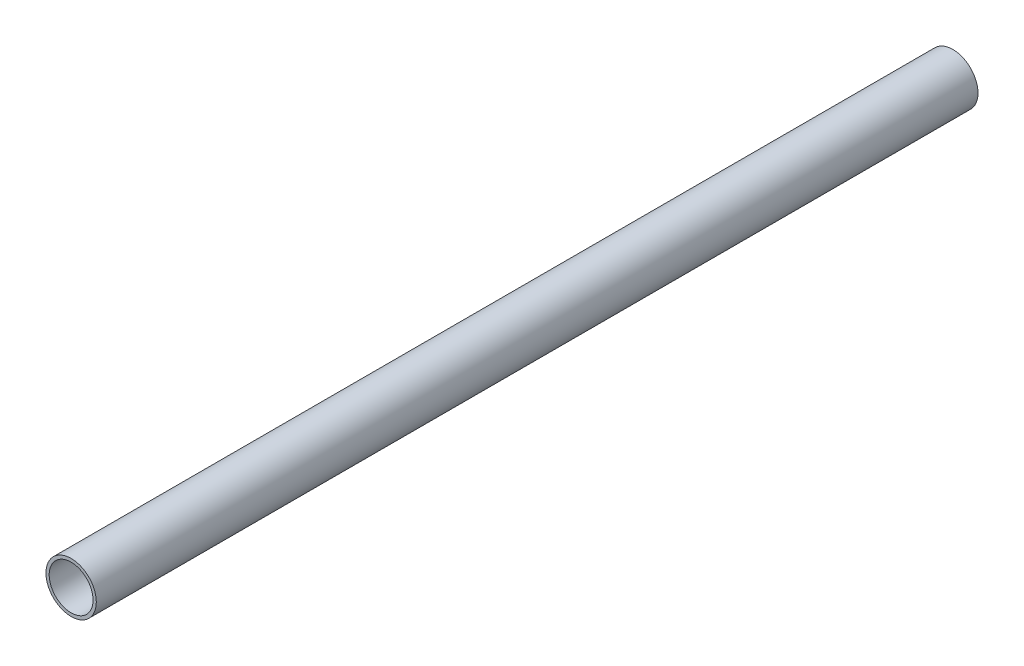
SolidWorks part; units mm, degrees
material "6061 Alloy"
ref_plane "Front Plane" through (0, 0, 0) normal (0, 0, 1) x (1, 0, 0)
ref_plane "Top Plane" through (0, 0, 0) normal (0, 1, 0) x (1, 0, 0)
ref_plane "Right Plane" through (0, 0, 0) normal (1, 0, 0) x (0, 0, -1)
sketch "Sketch1" plane through (0, 0, 0) normal (0, 0, 1) x (1, 0, 0)
  line L0 (-6.35, 0) -> (6.35, 0) construction
  line L1 (0, 0) -> (0, 1.0456) construction
  point P0 (-5.5372, 0)
  point P4 (0, 0)
  point P6 (5.5372, 0)
  dimension "OD" = 12.7
  dimension "ID" = 11.0744
sketch "Sketch2" plane through (0, 0, 0) normal (0, 0, 1) x (1, 0, 0)
  line L0 (-6.35, 0) -> (6.35, 0) construction
  circle A0 centre (0, 0) radius 5.5372
  circle A1 centre (0, 0) radius 6.35
  dimension "D1" = 11.0744
  dimension "D2" = 12.7
extrude "Boss-Extrude1" add sketch "Sketch2" along normal mid plane 222.377
sketch "Sketch3" plane through (0, 0, 0) normal (1, 0, 0) x (0, 0, -1)
  line L0 (111.1885, 0) -> (-111.1885, 0) construction
  line L1 (-111.1885, 6.35) -> (-111.1885, -6.35) construction
  line L2 (0, 0) -> (0, 21.8825) construction
  point P0 (-110.0766, 0)
  point P6 (0, 0)
  point P8 (110.0766, 0)
  dimension "D1" = 220.1532
ref_axis "Center Axis 1" through (0, 0, 111.1885) along (0, 0, -1)
ref_plane "Contact Plane 1" through (0, 0, 111.1885) normal (0, 0, 1) x (1, 0, 0)
ref_plane "Contact Plane 2" through (0, 0, -111.1885) normal (0, 0, -1) x (-1, 0, 0)
equation "\"D1@Sketch2\"=\"ID@Sketch1\""
equation "\"D2@Sketch2\"=\"OD@Sketch1\""
equation "\"D1@Sketch3\"=\"Length@Boss-Extrude1\"*0.99"
